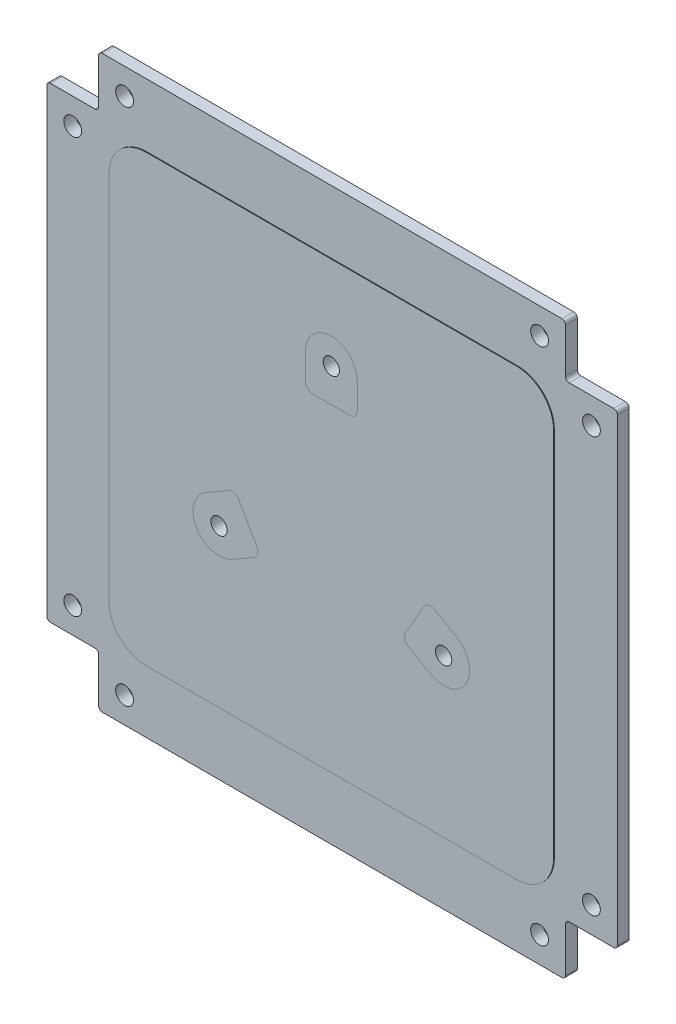
SolidWorks part; units mm, degrees
material "PET"
ref_plane "Front Plane" through (0, 0, 0) normal (0, 0, 1) x (1, 0, 0)
ref_plane "Top Plane" through (0, 0, 0) normal (0, 1, 0) x (1, 0, 0)
ref_plane "Right Plane" through (0, 0, 0) normal (1, 0, 0) x (0, 0, -1)
sketch "Sketch1" plane through (0, 0, 0) normal (0, 0, 1) x (1, 0, 0)
  line L0 (-31.5, 38) -> (-31.5, 32)
  line L1 (-31, -38.5) -> (31, -38.5)
  line L2 (-38.5, 31) -> (-38.5, -31)
  line L3 (-31, 38.5) -> (31, 38.5)
  line L4 (38.5, -31) -> (38.5, 31)
  line L5 (31.5, -38) -> (31.5, -32)
  line L6 (32, -31.5) -> (38, -31.5)
  line L7 (-32, 31.5) -> (-38, 31.5)
  line L8 (31.5, 38) -> (31.5, 32)
  line L9 (32, 31.5) -> (38, 31.5)
  line L10 (-38, -31.5) -> (-32, -31.5)
  line L11 (-31.5, -32) -> (-31.5, -38)
  line L12 (-32, -32) -> (32, 32) construction
  line L13 (32, -32) -> (-32, 32) construction
  arc A0 (-31, 38.5) -> (-31.5, 38) centre (-31, 38) ccw
  arc A1 (31, 38.5) -> (31.5, 38) centre (31, 38) cw
  arc A2 (31.5, 32) -> (32, 31.5) centre (32, 32) ccw
  arc A3 (38, 31.5) -> (38.5, 31) centre (38, 31) cw
  arc A4 (31, -38.5) -> (31.5, -38) centre (31, -38) ccw
  arc A5 (32, -31.5) -> (31.5, -32) centre (32, -32) ccw
  arc A6 (38, -31.5) -> (38.5, -31) centre (38, -31) ccw
  arc A7 (-31.5, -38) -> (-31, -38.5) centre (-31, -38) ccw
  arc A8 (-31.5, -32) -> (-32, -31.5) centre (-32, -32) ccw
  arc A9 (-38.5, -31) -> (-38, -31.5) centre (-38, -31) ccw
  arc A10 (-38, 31.5) -> (-38.5, 31) centre (-38, 31) ccw
  arc A11 (-32, 31.5) -> (-31.5, 32) centre (-32, 32) ccw
  point P0 (0, 0)
  dimension "D4" = 0.5
  dimension "D1" = 7
  dimension "D2" = 7
  dimension "D3" = 7
  dimension "D5" = 7
  dimension "D6" = 7
  dimension "D7" = 7
  dimension "D8" = 7
  dimension "D9" = 7
  dimension "D10" = 77
  dimension "D11" = 77
extrude "Boss-Extrude1" add sketch "Sketch1" along normal blind 1.6
sketch "Esboço1" plane through (0, 0, 1.6) normal (0, 0, 1) x (1, 0, 0)
  line L1 (-25, -30) -> (25, -30)
  line L2 (-30, -25) -> (-30, 25)
  line L3 (-25, 30) -> (25, 30)
  line L4 (30, -25) -> (30, 25)
  line L5 (-25, -25) -> (25, 25) construction
  line L6 (-25, 25) -> (25, -25) construction
  arc A0 (-30, 25) -> (-25, 30) centre (-25, 25) cw
  arc A1 (25, 30) -> (30, 25) centre (25, 25) cw
  arc A2 (30, -25) -> (25, -30) centre (25, -25) cw
  arc A3 (-25, -30) -> (-30, -25) centre (-25, -25) cw
  point P0 (0, 0)
  dimension "D1" = 5
  dimension "D2" = 60
  dimension "D3" = 60
extrude "Boss-Extrude2" add sketch "Esboço1" along normal blind 0.1
hole_wizard "M2 Hole1-FixingStructure" positions "Sketch3" profile "Sketch2" hole size "M2" standard "DIN"
sketch "Sketch3" plane through (0, 0, 0) normal (0, 0, -1) x (-1, 0, 0)
  line L0 (-31, 38.5) -> (31, 38.5) construction
  line L1 (31, -38.5) -> (-31, -38.5) construction
  line L2 (-38.5, -31) -> (-38.5, 31) construction
  line L3 (38.5, 31) -> (38.5, -31) construction
  line L4 (-31, 38.5) -> (31, 38.5) construction
  line L5 (31, -38.5) -> (-31, -38.5) construction
  line L6 (38.5, 31) -> (38.5, -31) construction
  line L7 (-38.5, -31) -> (-38.5, 31) construction
  point P0 (-28, 35)
  point P2 (28, 35)
  point P4 (-28, -35)
  point P6 (28, -35)
  point P20 (35, 28)
  point P22 (35, -28)
  point P24 (-35, -28)
  point P26 (-35, 28)
  dimension "D1" = 3.5
  dimension "D2" = 3.5
  dimension "D3" = 10.5
  dimension "D4" = 10.5
  dimension "D5" = 10.5
  dimension "D6" = 10.5
  dimension "D7" = 3.5
  dimension "D8" = 3.5
sketch "Sketch2" plane through (28, 35, 0) normal (1, 0, 0) x (0, 1, 0)
  line L0 (0, 0) -> (0, 200.721)
  line L1 (0, 200.721) -> (1.2, 200)
  line L2 (1.2, 200) -> (1.2, 0)
  line L5 (1.2, 0) -> (0, 0)
  line L10 (0, 200.721) -> (-1.2, 200) construction
  line L11 (0, -6.35) -> (0, 107.95) construction
  dimension "Hole Dia." = 2.4
  dimension "Hole Depth" = 200
  dimension "Drill Angle" = 118
sketch "Sketch4" plane through (0, 0, 1.7) normal (0, 0, 1) x (1, 0, 0)
  line L22 (3.5, 17.5) -> (3.5, 14)
  line L23 (-16.9054, -5.7189) -> (-14.7404, -4.4689)
  line L24 (-11.2404, -10.5311) -> (-13.4054, -11.7811)
  line L25 (-16.9054, -5.7189) -> (-13.8744, -3.9689)
  line L26 (-10.3744, -10.0311) -> (-13.4054, -11.7811)
  line L27 (-12.5083, -4.3349) -> (-10.0083, -8.6651)
  line L28 (-12.5083, -4.3349) -> (-10.0083, -8.6651)
  line L29 (-3.5, 14) -> (-3.5, 17.5)
  line L30 (2.5, 13) -> (-2.5, 13)
  line L31 (13.4054, -11.7811) -> (10.3744, -10.0311)
  line L32 (13.8744, -3.9689) -> (16.9054, -5.7189)
  line L33 (10.0083, -8.6651) -> (12.5083, -4.3349)
  arc A8 (-13.8744, -3.9689) -> (-12.5083, -4.3349) centre (-13.3744, -4.8349) cw
  arc A9 (-16.9054, -5.7189) -> (-13.4054, -11.7811) centre (-15.1554, -8.75) ccw
  arc A10 (-16.9054, -5.7189) -> (-13.4054, -11.7811) centre (-15.1554, -8.75) ccw
  arc A11 (-10.3744, -10.0311) -> (-10.0083, -8.6651) centre (-10.8744, -9.1651) ccw
  arc A12 (3.5, 14) -> (2.5, 13) centre (2.5, 14) cw
  arc A13 (3.5, 17.5) -> (-3.5, 17.5) centre (0, 17.5) ccw
  arc A14 (-3.5, 14) -> (-2.5, 13) centre (-2.5, 14) ccw
  arc A15 (10.3744, -10.0311) -> (10.0083, -8.6651) centre (10.8744, -9.1651) cw
  arc A16 (13.4054, -11.7811) -> (16.9054, -5.7189) centre (15.1554, -8.75) ccw
  arc A17 (13.8744, -3.9689) -> (12.5083, -4.3349) centre (13.3744, -4.8349) ccw
  point P34 (0, 0)
  dimension "D3" = 1
  dimension "D1" = 1
  dimension "D2" = 1
  dimension "D4" = 3
split line "Split Line1"
sketch "Sketch5" plane through (0, 0, 1.7) normal (0, 0, 1) x (1, 0, 0)
  circle A0 centre (-15.1554, -8.75) radius 1.1 construction
  circle A1 centre (-15.1554, -8.75) radius 1.1
  circle A2 centre (15.1554, -8.75) radius 1.1 construction
  circle A3 centre (15.1554, -8.75) radius 1.1
  circle A4 centre (0, 17.5) radius 1.1 construction
  circle A5 centre (0, 17.5) radius 1.1
extrude "Cut-Extrude1" cut sketch "Sketch5" against normal up to surface (1.7 mm away) up to face at (26.8, 35, 0)
